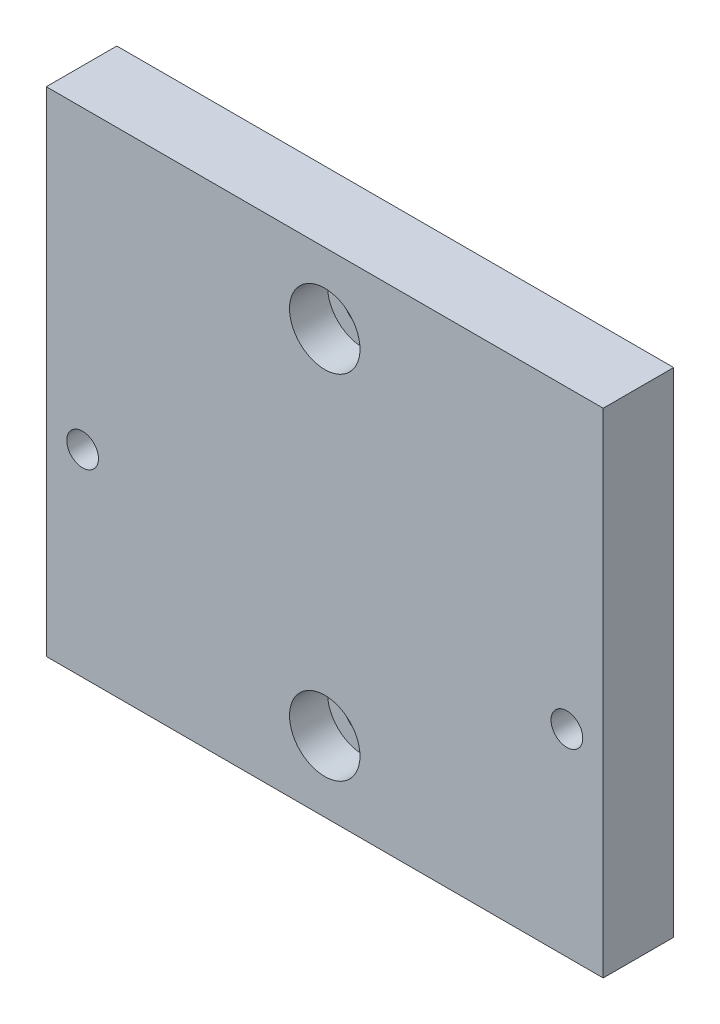
SolidWorks part; units mm, degrees
ref_plane "Top" through (0, 0, 0) normal (0, 0, 1) x (1, 0, 0)
ref_plane "Front" through (0, 0, 0) normal (0, 1, 0) x (1, 0, 0)
ref_plane "Right" through (0, 0, 0) normal (1, 0, 0) x (0, 0, -1)
sketch "Sketch1" plane through (0, 0, 0) normal (0, 0, 1) x (1, 0, 0)
  line L1 (0, 0) -> (79, 0)
  line L2 (0, 0) -> (0, 70)
  line L3 (0, 70) -> (79, 70)
  line L4 (79, 0) -> (79, 70)
  dimension "D1" = 79
  dimension "D2" = 70
extrude "Boss-Extrude1" add sketch "Sketch1" along normal blind 10
sketch "Sketch4" plane through (0, 0, 10) normal (0, 0, 1) x (1, 0, 0)
  line L0 (5.15, 28) -> (73.85, 28)
  line L2 (79, 0) -> (79, 70) construction
  line L5 (79, 70) -> (0, 70) construction
  point P2 (39.5, 28)
  dimension "D1" = 68.7
  dimension "D2" = 39.5
  dimension "D3" = 42
hole_wizard "M4 Clearance Hole1" positions "Sketch5" profile "Sketch6" hole size "M4" standard "DIN" end condition through all
sketch "Sketch5" plane through (0, 0, 10) normal (0, 0, 1) x (1, 0, 0)
  point P0 (5.15, 28)
  point P3 (73.85, 28)
sketch "Sketch6" plane through (5.15, 28, 10) normal (1, 0, 0) x (0, -1, 0)
  line L0 (0, 0) -> (0, 10)
  line L1 (0, 10) -> (2.25, 10)
  line L2 (2.25, 10) -> (2.25, 0)
  line L5 (2.25, 0) -> (0, 0)
  line L11 (0, -6.35) -> (0, 107.95) construction
  dimension "Thru Hole Dia." = 4.5
  dimension "Thru Hole Depth" = 10
sketch "Sketch11" plane through (0, 0, 0) normal (0, 0, -1) x (-1, 0, 0)
  line L0 (-79, 70) -> (0, 70) construction
  line L1 (-69.6353, 28) -> (-71.7427, 31.65)
  line L2 (-71.7427, 31.65) -> (-75.9573, 31.65)
  line L3 (-75.9573, 31.65) -> (-78.0647, 28)
  line L4 (-78.0647, 28) -> (-75.9573, 24.35)
  line L5 (-75.9573, 24.35) -> (-71.7427, 24.35)
  line L6 (-71.7427, 24.35) -> (-69.6353, 28)
  line L7 (-9.3647, 28) -> (-7.2573, 24.35)
  line L8 (-7.2573, 24.35) -> (-3.0427, 24.35)
  line L9 (-3.0427, 24.35) -> (-0.9353, 28)
  line L10 (-0.9353, 28) -> (-3.0427, 31.65)
  line L11 (-3.0427, 31.65) -> (-7.2573, 31.65)
  line L12 (-7.2573, 31.65) -> (-9.3647, 28)
  circle A0 centre (-73.85, 28) radius 3.65 construction
  circle A1 centre (-5.15, 28) radius 3.65 construction
  dimension "D1" = 7.3
  dimension "D2" = 7.3
extrude "Cut-Extrude3" cut sketch "Sketch11" against normal blind 3.5
sketch "Sketch12" plane through (0, 0, 10) normal (0, 0, -1) x (-1, 0, 0)
  line L0 (-39.5, 60) -> (-39.5, 10)
  line L1 (-79, 0) -> (-79, 70) construction
  line L2 (0, 0) -> (-79, 0) construction
  dimension "D1" = 39.5
  dimension "D2" = 50
  dimension "D3" = 10
hole_wizard "CBORE for M5 Socket Head Cap Screw1" positions "Sketch15" profile "Sketch16" counterbore size "M5" standard "DIN" end condition through all
sketch "Sketch15" plane through (0, 0, 10) normal (0, 0, 1) x (1, 0, 0)
  point P0 (39.5, 60)
  point P3 (39.5, 10)
sketch "Sketch16" plane through (39.5, 60, 10) normal (1, 0, 0) x (0, -1, 0)
  line L0 (0, 0) -> (0, 10)
  line L1 (0, 10) -> (2.75, 10)
  line L3 (2.75, 10) -> (2.75, 5.4)
  line L4 (2.75, 5.4) -> (5, 5.4)
  line L5 (5, 5.4) -> (5, 0)
  line L7 (5, 0) -> (0, 0)
  line L11 (0, -6.35) -> (0, 107.95) construction
  dimension "Thru Hole Dia." = 5.5
  dimension "Thru Hole Depth" = 10
  dimension "C'Bore Dia." = 10
  dimension "C'Bore Depth" = 5.4
